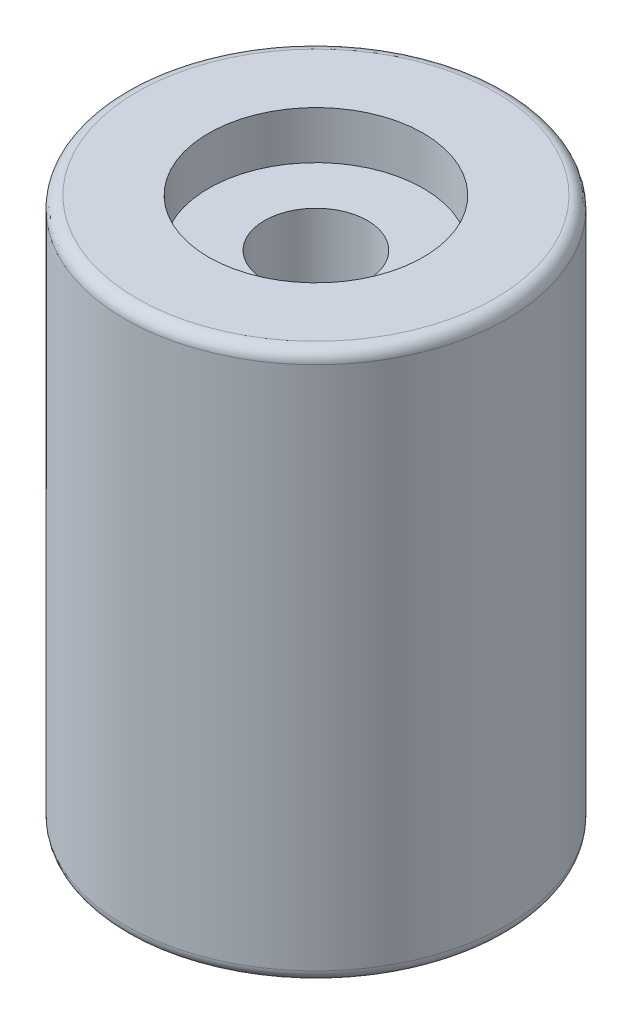
SolidWorks part; units mm, degrees
material "PET"
ref_plane "Front Plane" through (0, 0, 0) normal (0, 0, 1) x (1, 0, 0)
ref_plane "Top Plane" through (0, 0, 0) normal (0, 1, 0) x (1, 0, 0)
ref_plane "Right Plane" through (0, 0, 0) normal (1, 0, 0) x (0, 0, -1)
sketch "Sketch1" plane through (0, 0, 0) normal (0, 1, 0) x (1, 0, 0)
  circle A4 centre (0, 0) radius 25.4
  dimension "D1" = 50.8
extrude "Boss-Extrude1" add sketch "Sketch1" along normal blind 73.025 contours A4
fillet "Fillet1" radius 1.5875 2 edges at (0, 0, 25.4) (0, 73.025, 25.4)
sketch "Sketch2" plane through (0, 73.025, 0) normal (0, 1, 0) x (1, 0, 0)
  circle A0 centre (0, 0) radius 14.2875
  dimension "D1" = 28.575
extrude "Cut-Extrude1" cut sketch "Sketch2" against normal blind 6.35
sketch "Sketch3" plane through (0, 0, 0) normal (0, -1, 0) x (1, 0, 0)
  circle A0 centre (0, 0) radius 14.2875
  dimension "D1" = 28.575
extrude "Cut-Extrude2" cut sketch "Sketch3" against normal blind 6.35
sketch "Sketch4" plane through (0, 6.35, 0) normal (0, -1, 0) x (1, 0, 0)
  circle A0 centre (0, 0) radius 6.858
  dimension "D1" = 13.716
extrude "Cut-Extrude3" cut sketch "Sketch4" against normal through all and the other way through all
